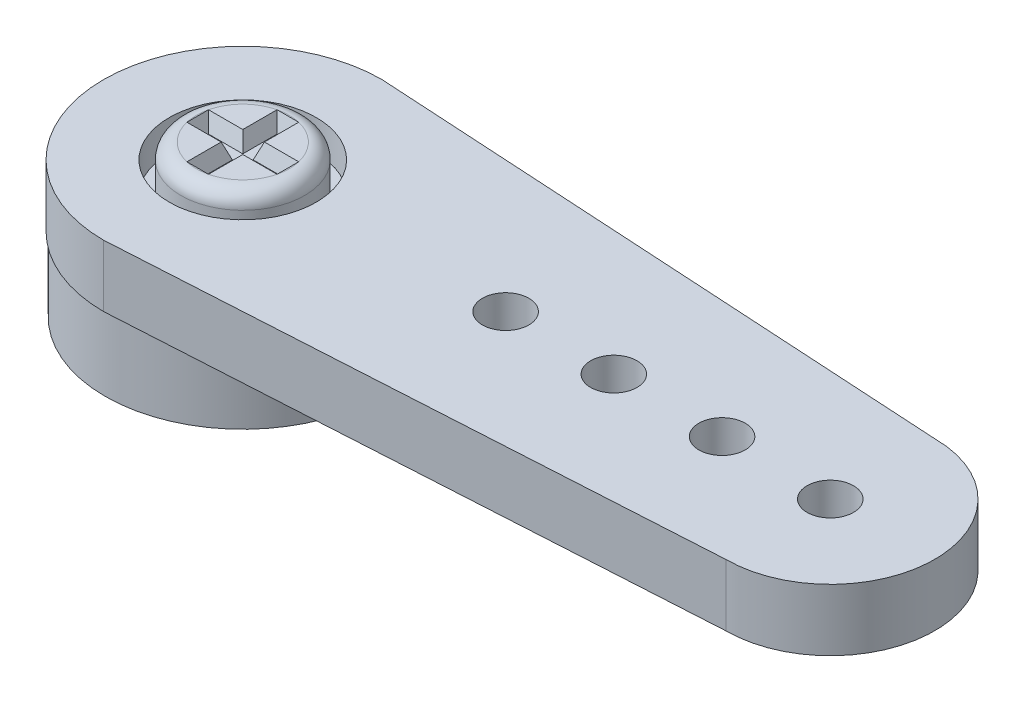
SolidWorks part; units mm, degrees
ref_plane "Frontale" through (0, 0, 0) normal (0, 0, 1) x (1, 0, 0)
ref_plane "Superiore" through (0, 0, 0) normal (0, 1, 0) x (1, 0, 0)
ref_plane "Destro" through (0, 0, 0) normal (1, 0, 0) x (0, 0, -1)
sketch "Sketch1" plane through (0, 0, 0) normal (0, 1, 0) x (1, 0, 0)
  line L0 (0, -4.5) -> (19, -3.3793)
  line L1 (0, 0) -> (19, 0) construction
  line L2 (0, 4.5) -> (19, 3.3793)
  circle A1 centre (0, 0) radius 2.375
  arc A2 (19, -3.3793) -> (19, 3.3793) centre (19, 0) ccw
  circle A3 centre (19, 0) radius 0.75
  circle A4 centre (15.5, 0) radius 0.75
  circle A5 centre (12, 0) radius 0.75
  circle A6 centre (0, 0) radius 1
  circle A7 centre (8.5, 0) radius 0.75
  circle A8 centre (0, 0) radius 4.45
  arc A9 (0, 4.5) -> (0, -4.5) centre (0, 0) ccw
  dimension "D1" = 4.75
  dimension "D4" = 1.5
  dimension "D6" = 2
  dimension "D7" = 8.9
  dimension "D3" = 19
  dimension "D5" = 4
extrude "Boss-Extrude1" add sketch "Sketch1" along normal blind 4.4 contours A1 A8 | A6 A1 region at (-2.3078, 0, 0) region at (-4.3241, 0, 0)
extrude "Boss-Extrude2" add sketch "Sketch1<3>" along normal up to surface (4.4 mm away) from offset 2.4 contours A1 L2 L0 | L0 A2 L2 A5 A3 region at (-4.4717, 0, 0) region at (-4.3241, 0, 0) up to face at (0, 4.4, 4.45)
sketch "Sketch1<3>" plane through (0, 0, 0) normal (0, 1, 0) x (1, 0, 0) same geometry as "Sketch1"
extrude "Cut-Extrude1" cut sketch "Sketch1<4>" against normal blind 1 from surface contours A1 starting at face at (0, 4.4, 1)
sketch "Sketch1<4>" plane through (0, 0, 0) normal (0, 1, 0) x (1, 0, 0) same geometry as "Sketch1"
sketch "Sketch2" plane through (0, 3.4, 0) normal (0, 1, 0) x (1, 0, 0)
  circle A0 centre (0, 0) radius 2
  dimension "D1" = 4
extrude "Boss-Extrude3" add sketch "Sketch2" along normal blind 1.5 separate body
fillet "Fillet1" radius 0.5 1 edges at (0, 4.9, 2)
sketch "Sketch3" plane through (0, 4.9, 0) normal (0, 1, 0) x (1, 0, 0)
  line L1 (0.35, -1.4586) -> (-0.35, -1.4586)
  line L2 (0.35, -1.4586) -> (0.35, 1.4586)
  line L3 (0.35, 1.4586) -> (-0.35, 1.4586)
  line L4 (-0.35, -1.4586) -> (-0.35, 1.4586)
  line L5 (0.35, -1.4586) -> (-0.35, 1.4586) construction
  line L6 (0.35, 1.4586) -> (-0.35, -1.4586) construction
  line L7 (1.4586, -0.35) -> (-1.4586, -0.35)
  line L8 (1.4586, -0.35) -> (1.4586, 0.35)
  line L9 (1.4586, 0.35) -> (-1.4586, 0.35)
  line L10 (-1.4586, -0.35) -> (-1.4586, 0.35)
  line L11 (1.4586, -0.35) -> (-1.4586, 0.35) construction
  line L12 (1.4586, 0.35) -> (-1.4586, -0.35) construction
  circle A0 centre (0, 0) radius 1.5 construction
  point P0 (0, 0)
  point P8 (0, 0)
  dimension "D1" = 0.7
extrude "Cut-Extrude2" cut sketch "Sketch3" against normal blind 0.5 draft 20 contours L4 L3 L2 L1 | L9 L10 L7 L8
sketch "Sketch4" plane through (0, 0, 0) normal (0, -1, 0) x (1, 0, 0)
  circle A0 centre (0, 0) radius 2.905
  dimension "D1" = 5.81
extrude "Cut-Extrude3" cut sketch "Sketch4" against normal blind 3
